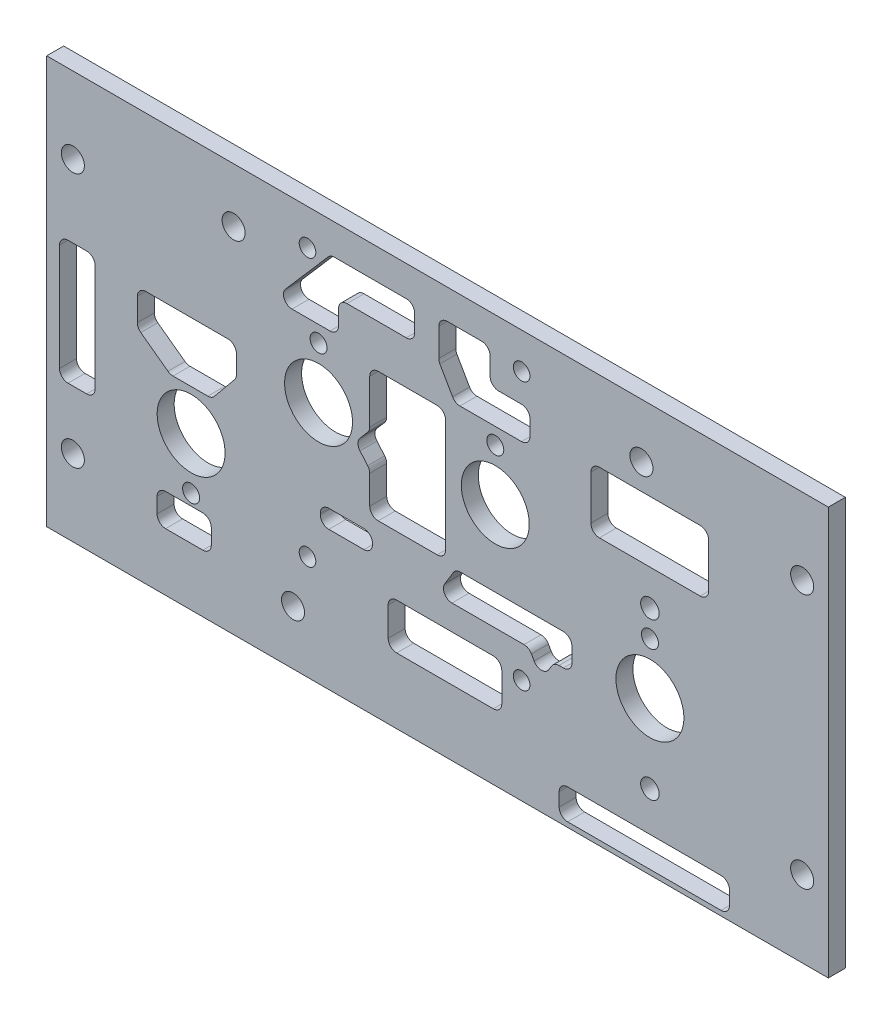
SolidWorks part; units mm, degrees
ref_plane "Front Plane" through (0, 0, 0) normal (0, 0, 1) x (1, 0, 0)
ref_plane "Top Plane" through (0, 0, 0) normal (0, 1, 0) x (1, 0, 0)
ref_plane "Right Plane" through (0, 0, 0) normal (1, 0, 0) x (0, 0, -1)
sketch "Sketch1" plane through (0, 0, 0) normal (0, 0, 1) x (1, 0, 0)
  line L4 (0, 76.2) -> (-146.05, 76.2)
  line L5 (-146.05, 76.2) -> (-146.05, 0)
  line L6 (-146.05, 0) -> (0, 0)
  line L7 (0, 0) -> (0, 76.2)
  line L8 (0, 76.2) -> (-146.05, 76.2)
  line L9 (-146.05, 76.2) -> (-146.05, 0)
  line L10 (-146.05, 0) -> (0, 0)
  line L11 (0, 0) -> (0, 76.2)
  dimension "D1" = 0
extrude "Boss-Extrude1" add sketch "Sketch1" against normal blind 3.175
hole_wizard "1/8 (0.125) Diameter Hole1" positions "Sketch3" profile "Sketch2" hole size "1/8" standard "ANSI Inch" end condition through all
sketch "Sketch3" plane through (0, 0, -3.175) normal (0, 0, -1) x (-1, 0, 0)
  circle A0 centre (95.25, 45.466) radius 9.652 construction
  circle A1 centre (119.0625, 28.575) radius 9.652 construction
  circle A2 centre (62.23, 45.466) radius 9.652 construction
  circle A3 centre (33.3375, 28.575) radius 9.652 construction
  point P0 (95.25, 55.118)
  point P4 (119.0625, 18.923)
  point P8 (62.23, 55.118)
  point P12 (33.3375, 38.227)
sketch "Sketch2" plane through (-95.25, 55.118, -3.175) normal (1, 0, 0) x (0, 1, 0)
  line L0 (0, 0) -> (0, 3.175)
  line L1 (0, 3.175) -> (1.5875, 3.175)
  line L2 (1.5875, 3.175) -> (1.5875, 0)
  line L5 (1.5875, 0) -> (0, 0)
  line L11 (0, -6.35) -> (0, 107.95) construction
  dimension "Thru Hole Dia." = 3.175
  dimension "Thru Hole Depth" = 3.175
hole_wizard "1/2 (0.5) Diameter Hole1" positions "Sketch5" profile "Sketch4" hole size "1/2" standard "ANSI Inch" end condition through all
sketch "Sketch5" plane through (0, 0, -3.175) normal (0, 0, -1) x (-1, 0, 0)
  point P0 (95.25, 45.466)
  point P3 (119.0625, 28.575)
  point P6 (62.23, 45.466)
  point P9 (33.3375, 28.575)
sketch "Sketch4" plane through (-95.25, 45.466, -3.175) normal (1, 0, 0) x (0, 1, 0)
  line L0 (0, 0) -> (0, 3.175)
  line L1 (0, 3.175) -> (6.35, 3.175)
  line L2 (6.35, 3.175) -> (6.35, 0)
  line L5 (6.35, 0) -> (0, 0)
  line L11 (0, -6.35) -> (0, 107.95) construction
  dimension "Thru Hole Dia." = 12.7
  dimension "Thru Hole Depth" = 3.175
hole_wizard "#6 Clearance Hole1" positions "Sketch7" profile "Sketch6" hole size "#6" standard "ANSI Inch" end condition through all
sketch "Sketch7" plane through (0, 0, -3.175) normal (0, 0, -1) x (-1, 0, 0)
  point P0 (141.1605, 61.9125)
  point P3 (141.1605, 14.2875)
  point P6 (4.8895, 61.9125)
  point P10 (4.8895, 14.2875)
  point P13 (111.125, 66.04)
  point P16 (100.015, 10.16)
  point P19 (34.925, 66.04)
sketch "Sketch6" plane through (-141.1605, 61.9125, -3.175) normal (1, 0, 0) x (0, 1, 0)
  line L0 (0, 0) -> (0, 3.175)
  line L1 (0, 3.175) -> (2.1526, 3.175)
  line L2 (2.1526, 3.175) -> (2.1526, 0)
  line L5 (2.1526, 0) -> (0, 0)
  line L11 (0, -6.35) -> (0, 107.95) construction
  dimension "Thru Hole Dia." = 4.3053
  dimension "Thru Hole Depth" = 3.175
hole_wizard "#4 Clearance Hole1" positions "Sketch9" profile "Sketch8" hole size "#4" standard "ANSI Inch" end condition through all
sketch "Sketch9" plane through (0, 0, -3.175) normal (0, 0, -1) x (-1, 0, 0)
  point P0 (33.3375, 43.18)
  point P3 (33.3375, 13.97)
sketch "Sketch8" plane through (-33.3375, 43.18, -3.175) normal (1, 0, 0) x (0, 1, 0)
  line L0 (0, 0) -> (0, 3.175)
  line L1 (0, 3.175) -> (1.7272, 3.175)
  line L2 (1.7272, 3.175) -> (1.7272, 0)
  line L5 (1.7272, 0) -> (0, 0)
  line L11 (0, -6.35) -> (0, 107.95) construction
  dimension "Thru Hole Dia." = 3.4544
  dimension "Thru Hole Depth" = 3.175
sketch "Sketch11" plane through (0, 0, -3.175) normal (0, 0, -1) x (-1, 0, 0)
  line L0 (23.9487, 61.26) -> (42.7833, 61.26)
  line L1 (44.3708, 59.6725) -> (44.3708, 51.4195)
  line L2 (22.3612, 59.6725) -> (22.3612, 51.4195)
  line L3 (23.9487, 49.832) -> (42.7833, 49.832)
  line L4 (64.7801, 70.6544) -> (71.2013, 70.6544)
  line L5 (72.7888, 69.0669) -> (72.7888, 63.8628)
  line L6 (72.5784, 63.0729) -> (70.2067, 58.9385)
  line L7 (68.8296, 58.1409) -> (57.3334, 58.1409)
  line L8 (55.7459, 59.7284) -> (55.7459, 62.5959)
  line L9 (63.1926, 69.0669) -> (63.1926, 65.7709)
  line L10 (61.6051, 64.1834) -> (57.3334, 64.1834)
  line L11 (78.8708, 70.4894) -> (92.27, 70.4894)
  line L12 (93.4697, 69.9417) -> (101.4203, 60.7681)
  line L13 (100.2206, 58.1409) -> (93.1099, 58.1409)
  line L14 (91.5224, 59.7284) -> (91.5224, 62.5791)
  line L15 (89.9349, 64.1666) -> (78.8708, 64.1666)
  line L16 (77.2833, 65.7541) -> (77.2833, 68.9019)
  line L17 (73.0966, 56.1163) -> (84.102, 56.1163)
  line L18 (85.6895, 54.5288) -> (85.6895, 46.3055)
  line L19 (86.0744, 45.2692) -> (87.505, 43.609)
  line L20 (87.5071, 41.5388) -> (86.0723, 39.8671)
  line L21 (85.6895, 38.8332) -> (85.6895, 33.5149)
  line L22 (84.102, 31.9274) -> (73.0966, 31.9274)
  line L23 (71.5091, 33.5149) -> (71.5091, 54.5288)
  line L24 (49.4951, 31.3075) -> (68.7282, 31.3075)
  line L25 (70.0828, 30.5478) -> (71.681, 27.9323)
  line L26 (70.3264, 25.517) -> (56.8566, 25.517)
  line L27 (55.4728, 24.7074) -> (54.969, 23.8112)
  line L28 (52.2305, 23.7613) -> (51.6843, 24.6551)
  line L29 (50.3297, 25.4149) -> (49.4951, 25.4149)
  line L30 (47.9076, 27.0024) -> (47.9076, 29.72)
  line L31 (138.5892, 48.3487) -> (142.062, 48.3487)
  line L32 (143.6495, 46.7612) -> (143.6495, 26.8106)
  line L33 (142.062, 25.2231) -> (138.5892, 25.2231)
  line L34 (137.0017, 26.8106) -> (137.0017, 46.7612)
  line L35 (112.188, 47.3287) -> (127.5281, 47.3287)
  line L36 (129.1156, 45.7412) -> (129.1156, 41.4887)
  line L37 (128.4662, 40.2081) -> (123.3903, 36.4895)
  line L38 (122.4521, 36.1826) -> (115.9411, 36.1826)
  line L39 (114.714, 36.7629) -> (110.9609, 41.3351)
  line L40 (110.6005, 42.3423) -> (110.6005, 45.7412)
  line L41 (20.051, 6.572) -> (48.7123, 6.572)
  line L42 (50.2998, 4.9845) -> (50.2998, 2.5039)
  line L43 (48.7123, 0.9164) -> (20.051, 0.9164)
  line L44 (18.4635, 2.5039) -> (18.4635, 4.9845)
  line L45 (116.8817, 16.8216) -> (123.8316, 16.8216)
  line L46 (125.4191, 15.2341) -> (125.4191, 12.383)
  line L47 (123.8316, 10.7955) -> (116.8817, 10.7955)
  line L48 (115.2942, 12.383) -> (115.2942, 15.2341)
  line L49 (86.7653, 29.3428) -> (93.3373, 29.3428)
  line L50 (94.9248, 27.7553) -> (94.9248, 27.5241)
  line L51 (85.1778, 27.7553) -> (85.1778, 27.5241)
  line L52 (86.7653, 25.9366) -> (93.3373, 25.9366)
  line L53 (62.6019, 20.8228) -> (80.6593, 20.8228)
  line L54 (82.2468, 19.2353) -> (82.2468, 13.8534)
  line L55 (61.0144, 19.2353) -> (61.0144, 13.8534)
  line L56 (62.6019, 12.2659) -> (80.6593, 12.2659)
  arc A0 (63.1926, 65.7709) -> (61.6051, 64.1834) centre (61.6051, 65.7709) cw
  arc A1 (64.7801, 70.6544) -> (63.1926, 69.0669) centre (64.7801, 69.0669) ccw
  arc A2 (71.2013, 70.6544) -> (72.7888, 69.0669) centre (71.2013, 69.0669) cw
  arc A3 (72.7888, 63.8628) -> (72.5784, 63.0729) centre (71.2013, 63.8628) cw
  arc A4 (70.2067, 58.9385) -> (68.8296, 58.1409) centre (68.8296, 59.7284) cw
  arc A5 (57.3334, 58.1409) -> (55.7459, 59.7284) centre (57.3334, 59.7284) cw
  arc A6 (55.7459, 62.5959) -> (57.3334, 64.1834) centre (57.3334, 62.5959) cw
  arc A7 (101.4203, 60.7681) -> (100.2206, 58.1409) centre (100.2206, 59.7284) cw
  arc A8 (93.1099, 58.1409) -> (91.5224, 59.7284) centre (93.1099, 59.7284) cw
  arc A9 (91.5224, 62.5791) -> (89.9349, 64.1666) centre (89.9349, 62.5791) ccw
  arc A10 (92.27, 70.4894) -> (93.4697, 69.9417) centre (92.27, 68.9019) cw
  arc A11 (78.8708, 70.4894) -> (77.2833, 68.9019) centre (78.8708, 68.9019) ccw
  arc A12 (78.8708, 64.1666) -> (77.2833, 65.7541) centre (78.8708, 65.7541) cw
  arc A13 (73.0966, 31.9274) -> (71.5091, 33.5149) centre (73.0966, 33.5149) cw
  arc A14 (85.6895, 33.5149) -> (84.102, 31.9274) centre (84.102, 33.5149) cw
  arc A15 (86.0723, 39.8671) -> (85.6895, 38.8332) centre (87.277, 38.8332) ccw
  arc A16 (85.6895, 46.3055) -> (86.0744, 45.2692) centre (87.277, 46.3055) ccw
  arc A17 (87.505, 43.609) -> (87.5071, 41.5388) centre (86.3024, 42.5727) cw
  arc A18 (84.102, 56.1163) -> (85.6895, 54.5288) centre (84.102, 54.5288) cw
  arc A19 (73.0966, 56.1163) -> (71.5091, 54.5288) centre (73.0966, 54.5288) ccw
  arc A20 (49.4951, 25.4149) -> (47.9076, 27.0024) centre (49.4951, 27.0024) cw
  arc A21 (51.6843, 24.6551) -> (50.3297, 25.4149) centre (50.3297, 23.8274) ccw
  arc A22 (54.969, 23.8112) -> (52.2305, 23.7613) centre (53.5851, 24.589) cw
  arc A23 (56.8566, 25.517) -> (55.4728, 24.7074) centre (56.8566, 23.9295) ccw
  arc A24 (71.681, 27.9323) -> (70.3264, 25.517) centre (70.3264, 27.1045) cw
  arc A25 (68.7282, 31.3075) -> (70.0828, 30.5478) centre (68.7282, 29.72) cw
  arc A26 (49.4951, 31.3075) -> (47.9076, 29.72) centre (49.4951, 29.72) ccw
  arc A28 (138.5892, 25.2231) -> (137.0017, 26.8106) centre (138.5892, 26.8106) cw
  arc A29 (143.6495, 26.8106) -> (142.062, 25.2231) centre (142.062, 26.8106) cw
  arc A30 (142.062, 48.3487) -> (143.6495, 46.7612) centre (142.062, 46.7612) cw
  arc A31 (138.5892, 48.3487) -> (137.0017, 46.7612) centre (138.5892, 46.7612) ccw
  arc A32 (110.9609, 41.3351) -> (110.6005, 42.3423) centre (112.188, 42.3423) cw
  arc A33 (115.9411, 36.1826) -> (114.714, 36.7629) centre (115.9411, 37.7701) cw
  arc A34 (123.3903, 36.4895) -> (122.4521, 36.1826) centre (122.4521, 37.7701) cw
  arc A35 (129.1156, 41.4887) -> (128.4662, 40.2081) centre (127.5281, 41.4887) cw
  arc A36 (127.5281, 47.3287) -> (129.1156, 45.7412) centre (127.5281, 45.7412) cw
  arc A37 (112.188, 47.3287) -> (110.6005, 45.7412) centre (112.188, 45.7412) ccw
  arc A38 (20.051, 0.9164) -> (18.4635, 2.5039) centre (20.051, 2.5039) cw
  arc A39 (50.2998, 2.5039) -> (48.7123, 0.9164) centre (48.7123, 2.5039) cw
  arc A40 (48.7123, 6.572) -> (50.2998, 4.9845) centre (48.7123, 4.9845) cw
  arc A41 (20.051, 6.572) -> (18.4635, 4.9845) centre (20.051, 4.9845) ccw
  arc A42 (123.8316, 16.8216) -> (125.4191, 15.2341) centre (123.8316, 15.2341) cw
  arc A43 (125.4191, 12.383) -> (123.8316, 10.7955) centre (123.8316, 12.383) cw
  arc A44 (116.8817, 10.7955) -> (115.2942, 12.383) centre (116.8817, 12.383) cw
  arc A45 (116.8817, 16.8216) -> (115.2942, 15.2341) centre (116.8817, 15.2341) ccw
  arc A46 (42.7833, 61.26) -> (44.3708, 59.6725) centre (42.7833, 59.6725) cw
  arc A47 (44.3708, 51.4195) -> (42.7833, 49.832) centre (42.7833, 51.4195) cw
  arc A48 (22.3612, 51.4195) -> (23.9487, 49.832) centre (23.9487, 51.4195) ccw
  arc A49 (23.9487, 61.26) -> (22.3612, 59.6725) centre (23.9487, 59.6725) ccw
  arc A50 (93.3373, 29.3428) -> (94.9248, 27.7553) centre (93.3373, 27.7553) cw
  arc A51 (94.9248, 27.5241) -> (93.3373, 25.9366) centre (93.3373, 27.5241) cw
  arc A52 (85.1778, 27.5241) -> (86.7653, 25.9366) centre (86.7653, 27.5241) ccw
  arc A53 (86.7653, 29.3428) -> (85.1778, 27.7553) centre (86.7653, 27.7553) ccw
  arc A54 (80.6593, 20.8228) -> (82.2468, 19.2353) centre (80.6593, 19.2353) cw
  arc A55 (82.2468, 13.8534) -> (80.6593, 12.2659) centre (80.6593, 13.8534) cw
  arc A56 (61.0144, 13.8534) -> (62.6019, 12.2659) centre (62.6019, 13.8534) ccw
  arc A57 (62.6019, 20.8228) -> (61.0144, 19.2353) centre (62.6019, 19.2353) ccw
  circle A58 centre (57.3085, 69.5024) radius 1.55
  circle A59 centre (97.3164, 69.5024) radius 1.55
  circle A60 centre (57.3085, 19.5082) radius 1.55
  circle A61 centre (97.3164, 19.5082) radius 1.55
  point P179 (98.9168, 68.9019)
  point P180 (97.9101, 68.9019)
  point P181 (97.7039, 69.528)
  point P182 (97.3738, 69.4867)
  point P183 (97.2604, 69.4764)
  point P184 (97.3641, 69.502)
  point P185 (97.3376, 69.5024)
  point P186 (97.3164, 69.5024)
  point P187 (59.4842, 68.9019)
  point P188 (58.3396, 69.5024)
  point P189 (57.7439, 69.5024)
  point P190 (56.9585, 69.5024)
  point P191 (57.1908, 69.5024)
  point P192 (57.3334, 69.5024)
  point P193 (57.2847, 69.5024)
  point P194 (57.3085, 69.5024)
  point P195 (97.3164, 16.8216)
  point P196 (97.3164, 17.8971)
  point P197 (97.3164, 19.2353)
  point P198 (97.3164, 19.5612)
  point P199 (97.3164, 19.5082)
  point P200 (0, 0)
  point P201 (56.8566, 19.2353)
  point P202 (57.3334, 19.5082)
  point P203 (57.274, 19.5082)
  point P204 (57.2922, 19.5082)
  point P205 (57.3085, 19.5082)
  dimension "D1" = 1.5875
  dimension "D2" = 1.5875
  dimension "D3" = 1.5875
  dimension "D4" = 1.5875
  dimension "D5" = 3.1
  dimension "D6" = 1.5875
  dimension "D7" = 1.5875
  dimension "D8" = 1.5875
  dimension "D9" = 1.5875
  dimension "D10" = 1.5875
  dimension "D11" = 3.1
  dimension "D12" = 3.1
  dimension "D13" = 3.1
extrude "Backlighting LED Holes" cut sketch "Sketch11" against normal through all
